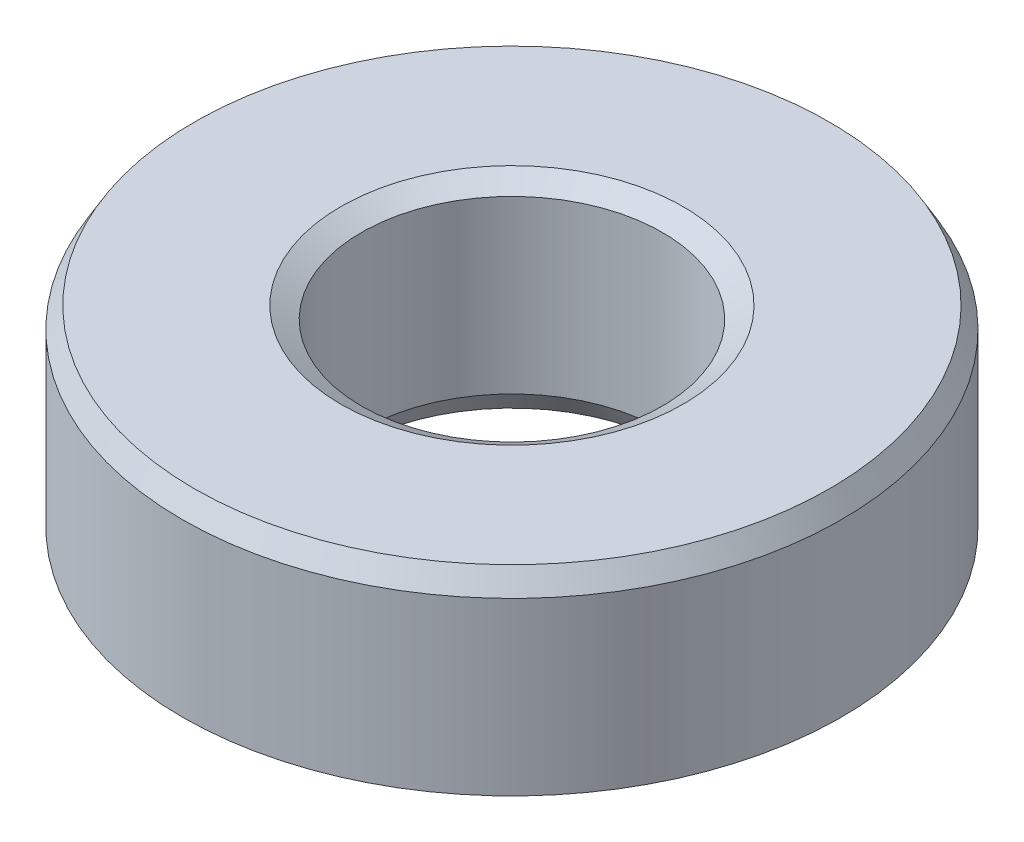
SolidWorks part; units mm, degrees
ref_plane "Front Plane" through (0, 0, 0) normal (0, 0, 1) x (1, 0, 0)
ref_plane "Top Plane" through (0, 0, 0) normal (0, 1, 0) x (1, 0, 0)
ref_plane "Right Plane" through (0, 0, 0) normal (1, 0, 0) x (0, 0, -1)
sketch "Sketch1" plane through (0, 0, 0) normal (0, 1, 0) x (1, 0, 0)
  circle A0 centre (0, 0) radius 20
  dimension "SLEEVE_OD" = 40
extrude "Boss-Extrude1" add sketch "Sketch1" along normal blind 12.3678
sketch "Sketch2" plane through (0, 0, 0) normal (0, 1, 0) x (1, 0, 0)
  circle A0 centre (0, 0) radius 9.1303
  dimension "BORE_D" = 18.2606
extrude "Cut-Extrude1" cut sketch "Sketch2" along normal through all
chamfer "Chamfer1" distance 1.2589 angle 30 4 edges at (0, 12.3678, 9.1303) (0, 0, 9.1303) (0, 0, 20) (0, 12.3678, 20) first distance on face at (0, 12.3678, 9.1303) first distance on face at (0, 0, 9.1303) first distance on face at (0, 12.3678, 20)
